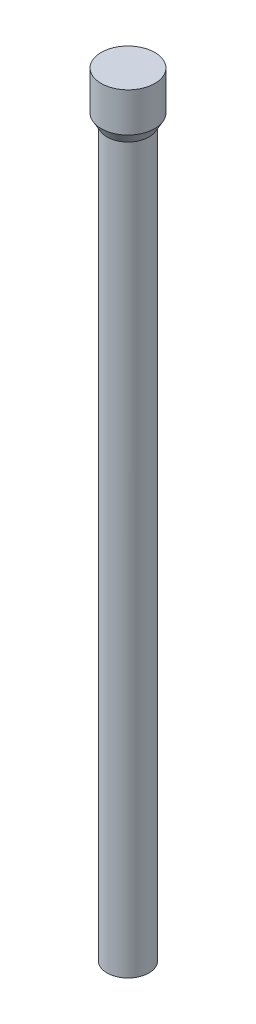
SolidWorks part; units mm, degrees
ref_plane "前视基准面" through (0, 0, 0) normal (0, 0, 1) x (1, 0, 0)
ref_plane "上视基准面" through (0, 0, 0) normal (0, 1, 0) x (1, 0, 0)
ref_plane "右视基准面" through (0, 0, 0) normal (1, 0, 0) x (0, 0, -1)
other "Configuration Table"
sketch "草图1" plane through (0, 0, 0) normal (0, 1, 0) x (1, 0, 0)
  circle A0 centre (0, 0) radius 2.5
  circle A1 centre (0, 0) radius 2
extrude "凸台-拉伸1" add sketch "草图1" along normal blind 2 contours A0
sketch "草图2" plane through (0, 0, 0) normal (0, -1, 0) x (1, 0, 0)
  circle A0 centre (0, 0) radius 1.95
extrude "凸台-拉伸2" add sketch "草图2" along normal blind 70
chamfer "倒角1" distance 1.5 angle 60 1 edges at (0, 0, -1.95) first distance on face at (0, 0, -1.95)
